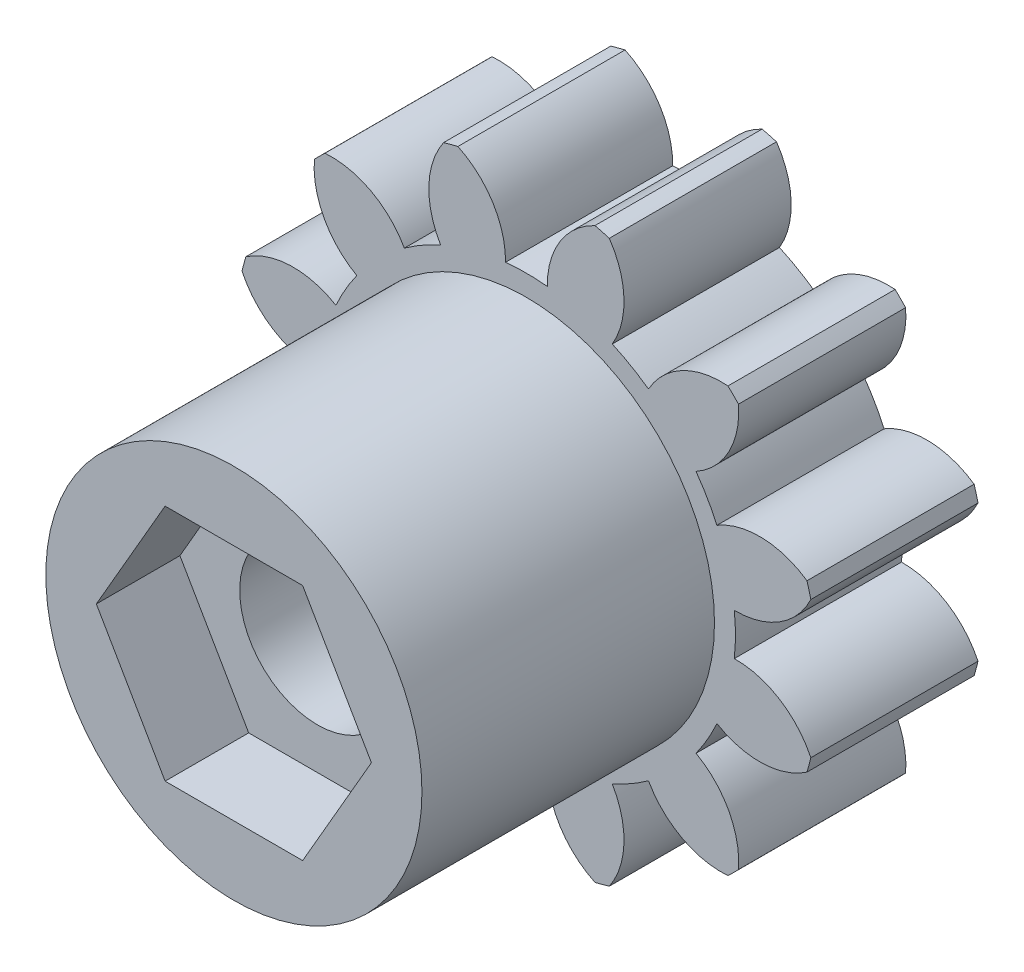
SolidWorks part; units mm, degrees
ref_plane "Front" through (0, 0, 0) normal (0, 0, 1) x (1, 0, 0)
ref_plane "Top" through (0, 0, 0) normal (0, 1, 0) x (1, 0, 0)
ref_plane "Right" through (0, 0, 0) normal (1, 0, 0) x (0, 0, -1)
sketch "Sketch1" plane through (0, 0, 0) normal (0, 0, 1) x (1, 0, 0)
  circle A0 centre (0, 0) radius 1
  circle A1 centre (0, 0) radius 7
extrude "Boss-Extrude1" add sketch "Sketch1" along normal blind 4
sketch "Sketch4" plane through (0, 0, 0) normal (0, 0, 1) x (1, 0, 0)
  line L0 (0, 5) -> (2.5, 5) construction
  line L1 (0, 5) -> (-2.5, 5) construction
  circle A0 centre (0, 0) radius 5
  circle A1 centre (0, 0) radius 7.5
  circle A2 centre (2.5, 5) radius 2
  circle A3 centre (-2.5, 5) radius 2
extrude "Cut-Extrude2" cut sketch "Sketch4" along normal through all contours A3 A0 A2 A1 region at (0, 6.5625, 0)
pattern_circular "CirPattern2" count 12 over 360 about axis through (0, 0, 4) along (0, 0, -1) of "Cut-Extrude2"
sketch "Sketch10" plane through (0, 0, 0) normal (0, 0, 1) x (1, 0, 0)
  line L0 (0, 4) -> (-5.1235, 4) construction
  line L1 (0, 4) -> (5.1235, 4) construction
  circle A0 centre (0, 0) radius 6.5
  circle A1 centre (0, 0) radius 4
  circle A2 centre (-2.5617, 4) radius 2.25
  circle A3 centre (2.5617, 4) radius 2.25
sketch "Sketch11" plane through (0, 0, 0) normal (0, 0, 1) x (1, 0, 0)
  circle A0 centre (0, 0) radius 4.5
extrude "Boss-Extrude2" add sketch "Sketch11" along normal blind 11
sketch "Sketch12" plane through (0, 0, 0) normal (0, 0, 1) x (1, 0, 0)
  line L1 (3.2909, 0) -> (1.6454, 2.85)
  line L2 (1.6454, 2.85) -> (-1.6454, 2.85)
  line L3 (-1.6454, 2.85) -> (-3.2909, 0)
  line L4 (-3.2909, 0) -> (-1.6454, -2.85)
  line L5 (-1.6454, -2.85) -> (1.6454, -2.85)
  line L6 (1.6454, -2.85) -> (3.2909, 0)
  circle A0 centre (0, 0) radius 2.85 construction
  dimension "D1" = 5.7
extrude "Cut-Extrude3" cut sketch "Sketch12" against normal blind 2 from offset 11
sketch "Sketch13" plane through (0, 0, 0) normal (0, 0, 1) x (1, 0, 0)
  line L0 (0, 0) -> (0, 0.95) construction
  line L2 (1.6, 0.95) -> (-1.6, 0.95)
  arc A0 (1.6, 0.95) -> (-1.6, 0.95) centre (0, 0) cw
extrude "Cut-Extrude4" cut sketch "Sketch13" along normal through all contours A0 L2 region at (0, -0.3098, 0)
